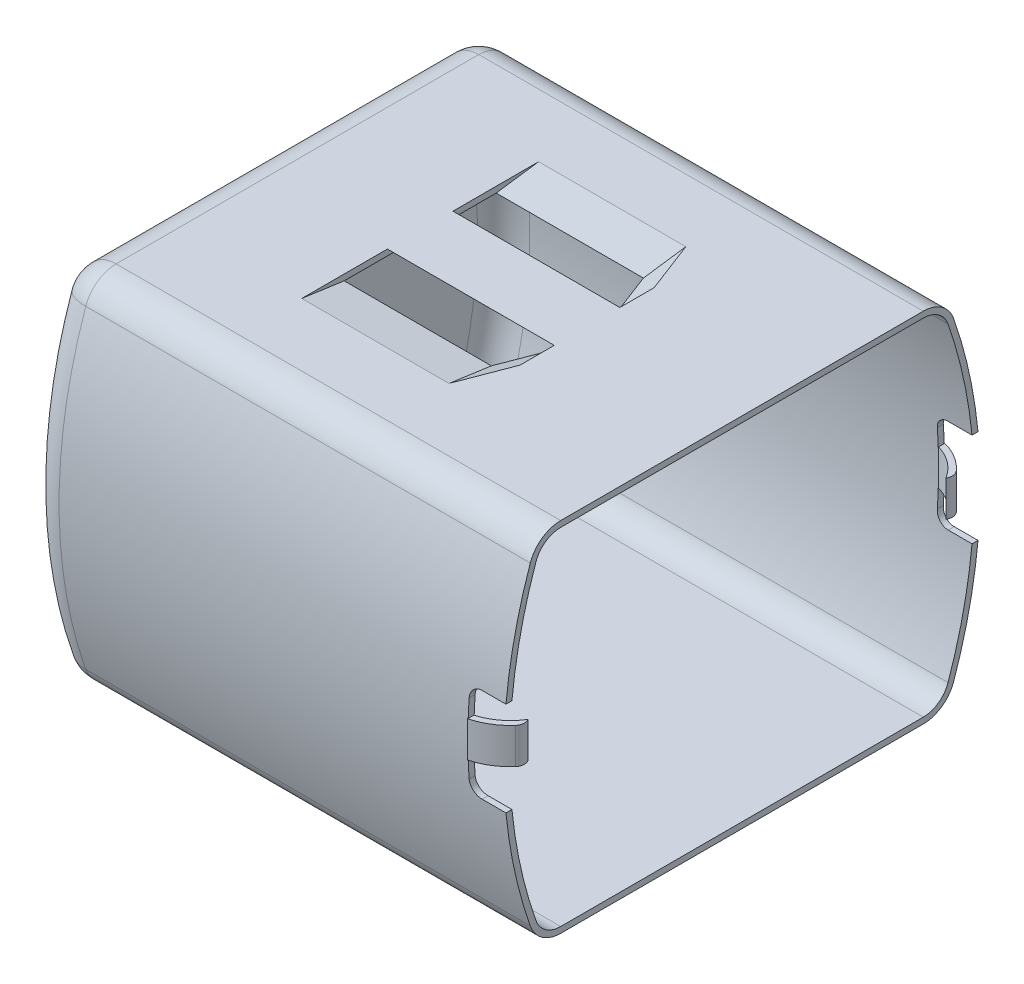
SolidWorks part; units mm, degrees
material "AISI Type A2 Tool Steel"
ref_plane "Front Plane" through (0, 0, 0) normal (0, 0, 1) x (1, 0, 0)
ref_plane "Top Plane" through (0, 0, 0) normal (0, 1, 0) x (1, 0, 0)
ref_plane "Right Plane" through (0, 0, 0) normal (1, 0, 0) x (0, 0, -1)
sketch "Sketch1" plane through (0, 0, 0) normal (1, 0, 0) x (0, 0, -1)
  line L1 (-8.5405, -7.5) -> (8.5405, -7.5)
  line L3 (-8.5405, 7.5) -> (8.5405, 7.5)
  line L5 (-8.5405, -7.5) -> (8.5405, 7.5) construction
  line L6 (-8.5405, 7.5) -> (8.5405, -7.5) construction
  arc A0 (8.5405, 7.5) -> (8.5405, -7.5) centre (-10, 0) cw
  arc A1 (-8.5405, -7.5) -> (-8.5405, 7.5) centre (10, 0) cw
  point P0 (0, 0)
  point P8 (10, 0)
  point P12 (-10, 0)
  dimension "D1" = 15
  dimension "D3" = 20
  dimension "D2" = 20
extrude "Boss-Extrude1" add sketch "Sketch1" along normal mid plane 20
sketch "Sketch2" plane through (-10, 0, 0) normal (-1, 0, 0) x (0, 0, 1)
  circle A0 centre (0, 0) radius 3
  dimension "D1" = 6
extrude "Boss-Extrude3" add sketch "Sketch2" along normal blind 1
sketch "Sketch3" plane through (-11, 0, 0) normal (-1, 0, 0) x (0, 0, 1)
  circle A0 centre (0, 0) radius 1
  dimension "D1" = 2
fillet "Fillet2" radius 1.35 8 edges at (0, -7.5, -8.5405) (0, -7.5, 8.5405) (0, 7.5, 8.5405) (0, 7.5, -8.5405) (-10, 0, 10) (-10, -7.5, 0) (-10, 0, -10) (-10, 7.5, 0)
shell "Shell6" thickness 0.25 removed face at (10, 0, 0)
extrude "Cut-Extrude2" cut sketch "Sketch3" against normal through all
ref_plane "Plane4" through (0, 1.3176, 9.3754) normal (0, -0.1392, -0.9903) x (-1, 0, 0)
sketch "Sketch8" plane through (0, 1.3176, 9.3754) normal (0, -0.1392, -0.9903) x (-1, 0, 0)
  line L0 (3.5, 6.7355) -> (3.5, 7.2355)
  line L1 (3.5, 7.2355) -> (-3.5, 7.2355)
  line L2 (-3.5, 7.2355) -> (-3.5, 7.0355)
  line L3 (-3.5, 7.0355) -> (-2.6758, 6.7355)
  line L4 (-2.6758, 6.7355) -> (3.5, 6.7355)
  point P6 (0, 7.2355)
  dimension "D1" = 0.5
  dimension "D2" = 0.2
  dimension "D3" = 7
  dimension "D4" = 7.2355
  dimension "D5" = 160
extrude "Cut-Extrude6" cut sketch "Sketch8" along normal blind 10
mirror "Mirror1" about plane through (0, 0, 0) normal (0, 0, 1) of "Cut-Extrude6"
sketch "Sketch9" plane through (0, 0, 0) normal (0, 0, 1) x (1, 0, 0)
  line L9 (10, -6.5952) -> (10, 6.5952) construction
  line L10 (10, 1.975) -> (9, 1.975)
  line L11 (10, 1.975) -> (10, -1.975)
  line L12 (10, -1.975) -> (9, -1.975)
  line L13 (8.5, 1.475) -> (8.5, -1.475)
  arc A0 (9, -1.975) -> (8.5, -1.475) centre (9, -1.475) cw
  arc A1 (9, 1.975) -> (8.5, 1.475) centre (9, 1.475) ccw
  point P6 (8.5, 0)
  dimension "D1" = 0.5
  dimension "D2" = 1.5
  dimension "D3" = 3.95
extrude "Cut-Extrude9" cut sketch "Sketch9" against normal through all both and the other way through all
sketch "Sketch10" plane through (0, 0, 0) normal (0, 1, 0) x (1, 0, 0)
  line L0 (9.7873, 8.7709) -> (10, 8.9022)
  line L1 (10, 8.6453) -> (10, 9.651) construction
  line L2 (9, 9.9022) -> (10, 9.9022) construction
  line L3 (8.5, 9.9455) -> (8.5, 10) construction
  line L4 (8.5, 9.9455) -> (8.5, 9.6948) construction
  line L5 (8.5, 9.75) -> (8.5, 10.0092)
  arc A0 (8.5, 10.0092) -> (10, 8.9022) centre (7.8725, 7.5893) cw
  arc A1 (8.5, 9.75) -> (9.7873, 8.7709) centre (7.8725, 7.5893) cw
  arc A2 (8.0229, 10.0847) -> (10, 8.9022) centre (7.8725, 7.5893) cw construction
  arc A3 (8.0079, 9.8352) -> (9.7873, 8.7709) centre (7.8725, 7.5893) cw construction
  dimension "D1" = 2.5
  dimension "D2" = 1
  dimension "D3" = 0.25
extrude "Boss-Extrude4" add sketch "Sketch10" along normal mid plane 1.5
fillet "Fillet3" radius 0.4 1 edges at (10, 0, -8.9022)
mirror "Mirror2" about plane through (0, 0, 0) normal (0, 0, 1) of "Fillet3", "Boss-Extrude4"
